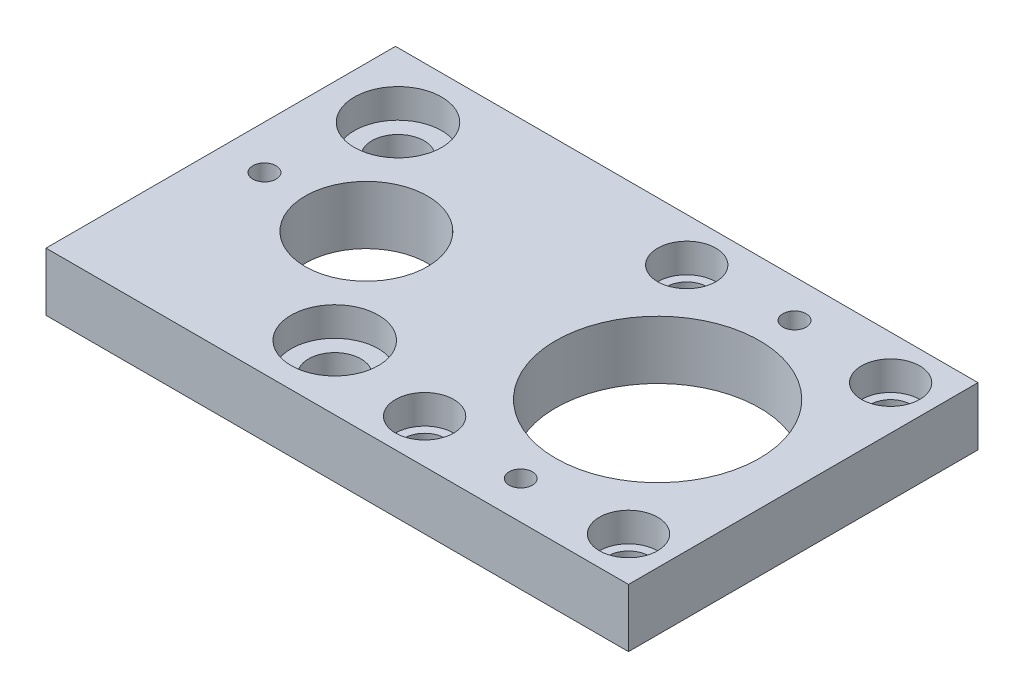
SolidWorks part; units mm, degrees
ref_plane "前视基准面" through (0, 0, 0) normal (0, 0, 1) x (1, 0, 0)
ref_plane "上视基准面" through (0, 0, 0) normal (0, 1, 0) x (1, 0, 0)
ref_plane "右视基准面" through (0, 0, 0) normal (1, 0, 0) x (0, 0, -1)
other "Configuration Table"
sketch "草图1" plane through (0, 0, 0) normal (0, 1, 0) x (1, 0, 0)
  line L1 (0, 0) -> (20, 0)
  line L2 (0, 0) -> (0, -12)
  line L3 (0, -12) -> (20, -12)
  line L4 (20, 0) -> (20, -12)
  circle A0 centre (5, -6) radius 2.1
  circle A4 centre (15, -6) radius 3.5
  circle A6 centre (7.8259, -8.9706) radius 0.6
  circle A7 centre (7.8259, -8.9706) radius 3.5
  circle A8 centre (9.8163, -3.6294) radius 2.6
  circle A9 centre (9.8163, -3.6294) radius 4.25
  circle A10 centre (15, -6) radius 4.25
  dimension "D2" = 4.2
  dimension "D3" = 5.7
  dimension "D6" = 8.5
  dimension "D4" = 20
  dimension "D5" = 7
  dimension "D7" = 7
  dimension "D14" = 1.2
  dimension "D15" = 5.2
  dimension "D17" = 8.5
  dimension "D8" = 4.1
  dimension "D9" = 5
  dimension "D10" = 6
  dimension "D11" = 12
  dimension "D12" = 5.7
  dimension "D13" = 10
  dimension "D16" = 3.0294
extrude "凸台-拉伸1" add sketch "草图1" along normal blind 2 contours L1 L4 L3 L2 | A0 | A4
sketch "草图2" plane through (0, 0, 0) normal (0, 1, 0) x (1, 0, 0)
  circle A0 centre (2.3, -2.2142) radius 1.5
  circle A1 centre (2.3, -2.2142) radius 0.9
  circle A2 centre (7.7, -9.7858) radius 1.5
  circle A3 centre (7.7, -9.7858) radius 0.9
  circle A4 centre (11.5, -1.5) radius 0.7
  circle A5 centre (11.5, -1.5) radius 1
  circle A6 centre (18.5, -10.5) radius 0.7
  circle A7 centre (18.5, -10.5) radius 1
  circle A8 centre (18.5, -1.5) radius 1
  circle A9 centre (18.5, -1.5) radius 0.7
  circle A10 centre (11.5, -10.5) radius 1
  circle A11 centre (11.5, -10.5) radius 0.7
  circle A20 centre (1.5, -6) radius 0.3
  circle A21 centre (16.5, -1.1) radius 0.3
  circle A22 centre (15, -10.9) radius 0.3
  point P22 (0, 0)
  point P25 (0, 0)
  dimension "D1" = 1.8
  dimension "D2" = 3
  dimension "D3" = 1.4
  dimension "D4" = 2
  dimension "D5" = 0.6
extrude "切除-拉伸1" cut sketch "草图2" along normal through all contours A1 | A3 | A11 | A6 | A9 | A4
extrude "切除-拉伸2" cut sketch "草图2<3>" against normal offset from surface (1 mm away) 1 from surface contours A0 | A2 up to face at (2.3, 0, 3.1142) starting at face at (2.3, 2, 3.1142)
sketch "草图2<3>" plane through (0, 0, 0) normal (0, 1, 0) x (1, 0, 0) same geometry as "草图2"
extrude "切除-拉伸3" cut sketch "草图2<4>" against normal offset from surface (1 mm away) 1 from surface contours A5 | A8 | A7 | A10 up to face at (2.3, 0, 3.1142) starting at face at (2.3, 2, 3.7142)
sketch "草图2<4>" plane through (0, 0, 0) normal (0, 1, 0) x (1, 0, 0) same geometry as "草图2"
sketch "草图5" plane through (5, -15.2, 6) normal (0, 1, 0) x (0, 0, -1)
  circle A0 centre (0, 3.5) radius 0.4
  circle A1 centre (-4.7, -10) radius 0.4
  circle A2 centre (4.7, -10) radius 0.4
  point P6 (0, 0)
  point P8 (0, 0)
  point P9 (0, 0)
  point P10 (-0.2627, -8.9535)
  dimension "D1" = 0.8
  dimension "D2" = 3.5
  dimension "D3" = 10
  dimension "D4" = 4.7
  dimension "D5" = 4.7
extrude "切除-拉伸4" cut sketch "草图5" along normal through all
